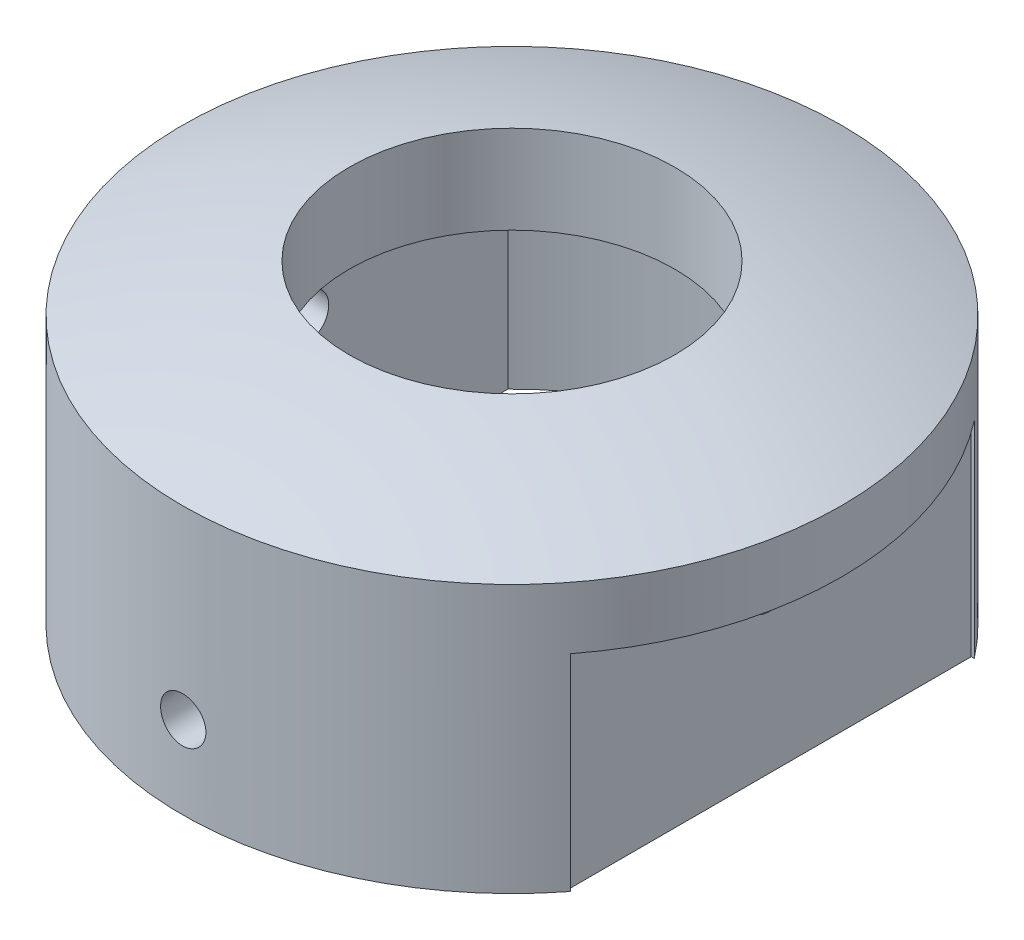
SolidWorks part; units mm, degrees
ref_plane "Alzado" through (0, 0, 0) normal (0, 0, 1) x (1, 0, 0)
ref_plane "Planta" through (0, 0, 0) normal (0, 1, 0) x (1, 0, 0)
ref_plane "Vista lateral" through (0, 0, 0) normal (1, 0, 0) x (0, 0, -1)
sketch "Croquis1" plane through (0, 0, 0) normal (0, 1, 0) x (1, 0, 0)
  circle A0 centre (0, 0) radius 16
  dimension "D1" = 32
extrude "Saliente-Extruir1" add sketch "Croquis1" along normal blind 13
shell "Vaciado1" thickness 2 removed face at (0, 0, 16)
sketch "Croquis2" plane through (0, 0, 0) normal (0, -1, 0) x (1, 0, 0)
  line L0 (10, 9.798) -> (17.7785, 9.798)
  line L1 (-10, -9.798) -> (10, -9.798) construction
  line L2 (-10, -9.798) -> (-10, 9.798)
  line L3 (-10, 9.798) -> (10, 9.798) construction
  line L4 (10, -9.798) -> (10, 9.798)
  line L5 (-10, -9.798) -> (10, 9.798) construction
  line L6 (-10, 9.798) -> (10, -9.798) construction
  line L7 (17.7785, 9.798) -> (17.7785, -9.798)
  line L8 (17.7785, -9.798) -> (10, -9.798)
  line L9 (-10, 9.798) -> (-18.9654, 9.798)
  line L10 (-18.9654, 9.798) -> (-18.9654, -9.798)
  line L11 (-18.9654, -9.798) -> (-10, -9.798)
  circle A0 centre (0, 0) radius 14 construction
  point P0 (0, 0)
  dimension "D1" = 20
extrude "Cortar-Extruir1" cut sketch "Croquis2" against normal blind 10
sketch "Croquis3" plane through (0, 0, 0) normal (0, -1, 0) x (1, 0, 0)
  line L0 (-10, 9.798) -> (-12.5, 9.798)
  line L1 (-10, -9.798) -> (10, -9.798) construction
  line L2 (-10, -9.798) -> (-10, 9.798)
  line L3 (-10, 9.798) -> (10, 9.798) construction
  line L4 (10, -9.798) -> (10, 9.798)
  line L5 (-10, -9.798) -> (10, 9.798) construction
  line L6 (-10, 9.798) -> (10, -9.798) construction
  line L7 (-10, 9.798) -> (-12.6491, 9.798) construction
  line L8 (-10, -9.798) -> (-12.5, -9.798)
  line L9 (-12.6491, -9.798) -> (-10, -9.798) construction
  line L10 (-12.5, 9.798) -> (-12.5, -9.798)
  line L11 (10, -9.798) -> (12.5, -9.798)
  line L12 (10, 9.798) -> (12.5, 9.798)
  line L13 (12.5, 9.798) -> (12.5, -9.798)
  point P0 (0, 0)
  dimension "D1" = 2.5
  dimension "D2" = 2.5
  dimension "D3" = 2.5
  dimension "D4" = 2.5
extrude "Saliente-Extruir2" add sketch "Croquis3" against normal through all
sketch "Croquis4" plane through (-12.5, 0, 0) normal (-1, 0, 0) x (0, 0, 1)
  line L0 (0, 9) -> (0, 11)
  line L1 (-6.3048, 11) -> (6.3048, 11) construction
  circle A0 centre (0, 7.9) radius 1.1
  dimension "D1" = 2.2
  dimension "D2" = 2
extrude "Cortar-Extruir2" cut sketch "Croquis4" against normal through all contours A0 region at (-12.5, 7.9, 0)
ref_plane "Plano1" through (0, 0, 26) normal (0, 0, 1) x (1, 0, 0)
sketch "Croquis5" plane through (0, 0, 26) normal (0, 0, 1) x (1, 0, 0)
  line L0 (0, 5.1) -> (0, 13)
  line L1 (16, 13) -> (-16, 13) construction
  circle A0 centre (0, 4) radius 1.1
  dimension "D2" = 2.2
  dimension "D1" = 7.9
extrude "Cortar-Extruir3" cut sketch "Croquis5" against normal through all contours A0
sketch "Croquis6" plane through (0, 13, 0) normal (0, 1, 0) x (1, 0, 0)
  circle A0 centre (0, 0) radius 16
dome "Cúpula1" faces to dome 1 distance 3 reverse direction no elliptical dome no face at (0, 13, 16) parameters "D1"=3
sketch "Croquis7" plane through (0, 11, 0) normal (0, -1, 0) x (1, 0, 0)
  circle A0 centre (0, 0) radius 7.9
  dimension "D1" = 15.8
extrude "Cortar-Extruir4" cut sketch "Croquis7" against normal blind 10
